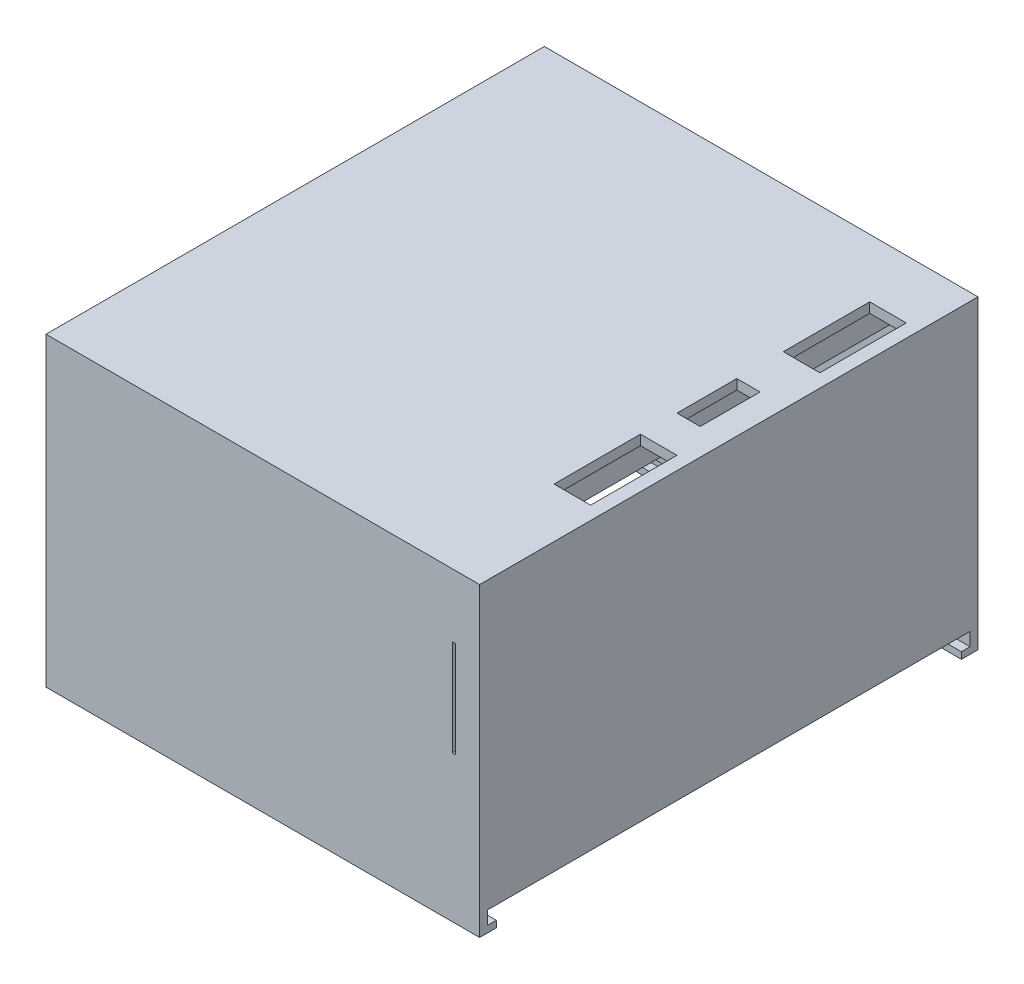
SolidWorks part; units mm, degrees
ref_plane "Front Plane" through (0, 0, 0) normal (0, 0, 1) x (1, 0, 0)
ref_plane "Top Plane" through (0, 0, 0) normal (0, 1, 0) x (1, 0, 0)
ref_plane "Right Plane" through (0, 0, 0) normal (1, 0, 0) x (0, 0, -1)
sketch "Sketch1" plane through (0, 0, 0) normal (0, 1, 0) x (1, 0, 0)
  line L1 (-32.63, -37.5) -> (32.63, -37.5)
  line L2 (-32.63, -37.5) -> (-32.63, 37.5)
  line L3 (-32.63, 37.5) -> (32.63, 37.5)
  line L4 (32.63, -37.5) -> (32.63, 37.5)
  point P5 (-32.63, 0)
  point P10 (0, -37.5)
  dimension "D1" = 75
  dimension "D2" = 65.26
extrude "Boss-Extrude1" add sketch "Sketch1" along normal blind 43
sketch "Sketch3" plane through (0, 0, 0) normal (0, 0, 1) x (1, 0, 0)
  line L0 (-32.63, 0) -> (32.63, 0) construction
  line L1 (30.63, 0) -> (-30.63, 0)
  line L4 (-30.63, 0) -> (-30.63, 31.95)
  line L5 (-32.63, 43) -> (-32.63, 0) construction
  line L6 (19.3, 41) -> (-32.63, 41) construction
  line L7 (7.61, 37) -> (4.28, 37)
  line L8 (-10.74, 37) -> (-14.07, 37)
  line L9 (-32.63, 43) -> (32.63, 43) construction
  line L10 (22.63, 37) -> (23.63, 37)
  line L11 (23.63, 37) -> (23.63, 41.5)
  line L12 (23.63, 41.5) -> (30.63, 41.5)
  line L13 (30.63, 41.5) -> (30.63, 0)
  arc A0 (-14.07, 37) -> (-30.63, 31.95) centre (-21.58, 31.95) ccw
  arc A1 (4.28, 37) -> (-10.74, 37) centre (-3.23, 31.95) ccw
  arc A2 (22.63, 37) -> (7.61, 37) centre (15.12, 31.95) ccw
  dimension "D3" = 18.1
  dimension "D4" = 0.25
  dimension "D5" = 0.25
  dimension "D6" = 6
  dimension "D1" = 2
  dimension "D2" = 2
  dimension "D7" = 1.5
  dimension "D8" = 1
  dimension "D9" = 7
extrude "Cut-Extrude1" cut sketch "Sketch3" against normal blind 35 and the other way blind 35
sketch "Sketch4" plane through (0, 0, 0) normal (0, -1, 0) x (-1, 0, 0)
  line L6 (-23.63, -35) -> (-23.63, 35) construction
  line L7 (-23.63, 36.7) -> (-30.63, 36.7)
  line L8 (-23.63, 36.7) -> (-23.63, 35)
  line L9 (-23.63, 35) -> (-30.63, 35)
  line L10 (-30.63, 36.7) -> (-30.63, 35)
  line L11 (-32.63, 37.5) -> (32.63, 37.5) construction
  dimension "D1" = 0.8
extrude "Cut-Extrude2" cut sketch "Sketch4" against normal up to surface (41.5 mm away) up to face at (27.13, 41.5, 0)
sketch "Sketch5" plane through (0, 41.5, 0) normal (0, -1, 0) x (-1, 0, 0)
  line L0 (-30.63, -35) -> (-30.63, 36.7) construction
  line L1 (-25.13, -5.8) -> (-30.63, -5.8)
  line L2 (-25.13, -5.8) -> (-25.13, -18.8)
  line L3 (-25.13, -18.8) -> (-30.63, -18.8)
  line L4 (-30.63, -5.8) -> (-30.63, -18.8)
  line L5 (-30.63, -35) -> (-30.63, 36.7) construction
  line L6 (-25.13, 28.7) -> (-30.63, 28.7)
  line L7 (-25.13, 28.7) -> (-25.13, 15.7)
  line L8 (-25.13, 15.7) -> (-30.63, 15.7)
  line L9 (-30.63, 28.7) -> (-30.63, 15.7)
  line L11 (-25.13, 8.7) -> (-28.63, 8.7)
  line L12 (-25.13, 8.7) -> (-25.13, -0.3)
  line L13 (-25.13, -0.3) -> (-28.63, -0.3)
  line L14 (-28.63, 8.7) -> (-28.63, -0.3)
  line L17 (-23.63, 36.7) -> (-30.63, 36.7) construction
  line L18 (-30.63, 36.7) -> (-23.63, 36.7) construction
  dimension "D1" = 8
  dimension "D2" = 21
  dimension "D3" = 28
  dimension "D4" = 37
  dimension "D5" = 42.5
  dimension "D6" = 55.5
  dimension "D7" = 5.5
  dimension "D8" = 5.5
  dimension "D9" = 2
extrude "Cut-Extrude3" cut sketch "Sketch5" against normal through all
sketch "Sketch7" plane through (0, 0, -36.7) normal (0, 0, 1) x (1, 0, 0)
  line L0 (30.63, 41.5) -> (25.13, 41.5) construction
  line L1 (23.63, 29.5) -> (30.63, 29.5)
  line L2 (23.63, 29.5) -> (23.63, 32)
  line L3 (23.63, 35.5) -> (30.63, 35.5)
  line L4 (30.63, 29.5) -> (30.63, 32)
  line L5 (30.63, 41.5) -> (23.63, 41.5) construction
  line L6 (30.63, 41.5) -> (30.63, 0) construction
  line L8 (25.13, 41.5) -> (28.63, 41.5) construction
  line L9 (26.13, 15.5) -> (29.03, 15.5)
  line L10 (26.13, 15.5) -> (26.13, 23.5)
  line L11 (26.13, 23.5) -> (29.03, 23.5)
  line L12 (29.03, 15.5) -> (29.03, 23.5)
  line L13 (23.63, 37) -> (23.63, 0) construction
  line L14 (23.63, 32.5) -> (31.13, 32.5) construction
  line L15 (23.63, 32) -> (24.9363, 32)
  line L17 (23.63, 33) -> (24.9363, 33)
  line L19 (29.3237, 32) -> (30.63, 32)
  line L21 (29.3237, 33) -> (30.63, 33)
  line L23 (23.63, 33) -> (23.63, 35.5)
  line L24 (30.63, 33) -> (30.63, 35.5)
  line L25 (30.63, 41.5) -> (30.63, 0) construction
  arc A0 (29.3237, 33) -> (24.9363, 33) centre (27.13, 32.5) ccw
  arc A1 (24.9363, 32) -> (29.3237, 32) centre (27.13, 32.5) ccw
  dimension "D4" = 4.5
  dimension "D1" = 6
  dimension "D2" = 12
  dimension "D3" = 3.5
  dimension "D5" = 18
  dimension "D6" = 2.9
  dimension "D7" = 1
  dimension "D8" = 26
  dimension "D9" = 1.6
extrude "Cut-Extrude4" cut sketch "Sketch7" against normal through all
sketch "Sketch8" plane through (0, 0, 0) normal (0, -1, 0) x (-1, 0, 0)
  line L1 (0, 0) -> (-45.2311, 0) construction
  line L2 (-30.63, -35) -> (-30.63, 36.7) construction
  line L3 (-30.63, 7) -> (-29.13, 7)
  line L4 (-30.63, 7) -> (-30.63, 13)
  line L5 (-30.63, 13) -> (-29.13, 13)
  line L8 (-30.63, -13) -> (-29.13, -13)
  line L9 (-30.63, -13) -> (-30.63, -7)
  line L10 (-30.63, -7) -> (-29.13, -7)
  arc A1 (-29.13, -13) -> (-29.13, -7) centre (-29.13, -10) ccw
  arc A2 (-29.13, 7) -> (-29.13, 13) centre (-29.13, 10) ccw
  dimension "D1" = 6
  dimension "D2" = 10
  dimension "D3" = 1.5
extrude "Boss-Extrude2" add sketch "Sketch8" against normal blind 10
sketch "Sketch11" plane through (0, 0, 0) normal (0, 0, 1) x (1, 0, 0)
  line L0 (30.63, 10) -> (26.13, 6)
  line L2 (26.13, 6) -> (26.13, 10)
  line L4 (26.13, 10) -> (30.63, 10)
  line L6 (26.13, 10) -> (26.13, 0) construction
  line L7 (30.63, 10) -> (29.13, 10) construction
  line L8 (30.63, 41.5) -> (30.63, 0) construction
  line L9 (30.63, 0) -> (-30.63, 0) construction
  dimension "D1" = 6
extrude "Cut-Extrude5" cut sketch "Sketch11" against normal blind 20 and the other way blind 20
sketch "Sketch13" plane through (0, 0, 0) normal (0, -1, 0) x (1, 0, 0)
  line L0 (32.63, 37.5) -> (32.63, -37.5) construction
  line L1 (32.63, -35) -> (26.13, -35)
  line L2 (32.63, -35) -> (32.63, 35)
  line L3 (32.63, 35) -> (26.13, 35)
  line L4 (26.13, -35) -> (26.13, 35)
  line L5 (-30.63, 35) -> (30.63, 35) construction
  line L6 (-30.63, -35) -> (23.63, -35) construction
  arc A0 (29.13, -7) -> (29.13, -13) centre (29.13, -10) ccw construction
sketch "Sketch14" plane through (0, 0, 37.5) normal (0, 0, 1) x (1, 0, 0)
  line L0 (-32.63, 43) -> (32.63, 43) construction
  line L1 (29.03, 19) -> (28.53, 19)
  line L2 (29.03, 19) -> (29.03, 33.5)
  line L3 (29.03, 33.5) -> (28.53, 33.5)
  line L4 (28.53, 19) -> (28.53, 33.5)
  line L5 (32.63, 43) -> (32.63, 0) construction
  dimension "D1" = 14.5
  dimension "D2" = 9.5
  dimension "D3" = 3.6
  dimension "D4" = 0.5
extrude "Cut-Extrude6" cut sketch "Sketch14" against normal up to next
sketch "Sketch15" plane through (0, 0, 0) normal (0, -1, 0) x (-1, 0, 0)
  line L0 (31.43, -36.3) -> (-32.63, -36.3)
  line L1 (-32.63, -37.5) -> (-32.63, 37.5) construction
  line L2 (-32.63, -36.3) -> (-32.63, -37.5)
  line L3 (-32.63, -37.5) -> (32.63, -37.5)
  line L4 (32.63, -37.5) -> (-32.63, -37.5) construction
  line L5 (32.63, -37.5) -> (32.63, 37.5)
  line L6 (-32.63, 37.5) -> (32.63, 37.5) construction
  line L7 (32.63, 37.5) -> (32.63, -37.5) construction
  line L8 (32.63, 37.5) -> (-32.63, 37.5)
  line L9 (-32.63, 37.5) -> (-32.63, 36.3)
  line L10 (-32.63, 36.3) -> (31.43, 36.3)
  line L11 (31.43, 36.3) -> (31.43, -36.3)
  dimension "D1" = 1.2
  dimension "D2" = 1.2
  dimension "D3" = 1.2
extrude "Boss-Extrude3" add sketch "Sketch15" along normal blind 2
sketch "Sketch16" plane through (0, -2, 0) normal (0, -1, 0) x (-1, 0, 0)
  line L0 (32.63, -37.5) -> (-32.63, -37.5)
  line L1 (-32.63, -37.5) -> (-32.63, -35)
  line L2 (-32.63, -35) -> (30.63, -35)
  line L3 (30.63, -35) -> (30.63, 35)
  line L4 (30.63, 35) -> (-32.63, 35)
  line L5 (-32.63, 35) -> (-32.63, 37.5)
  line L6 (-32.63, 37.5) -> (32.63, 37.5)
  line L7 (32.63, 37.5) -> (32.63, -37.5)
extrude "Boss-Extrude4" add sketch "Sketch16" along normal blind 1
